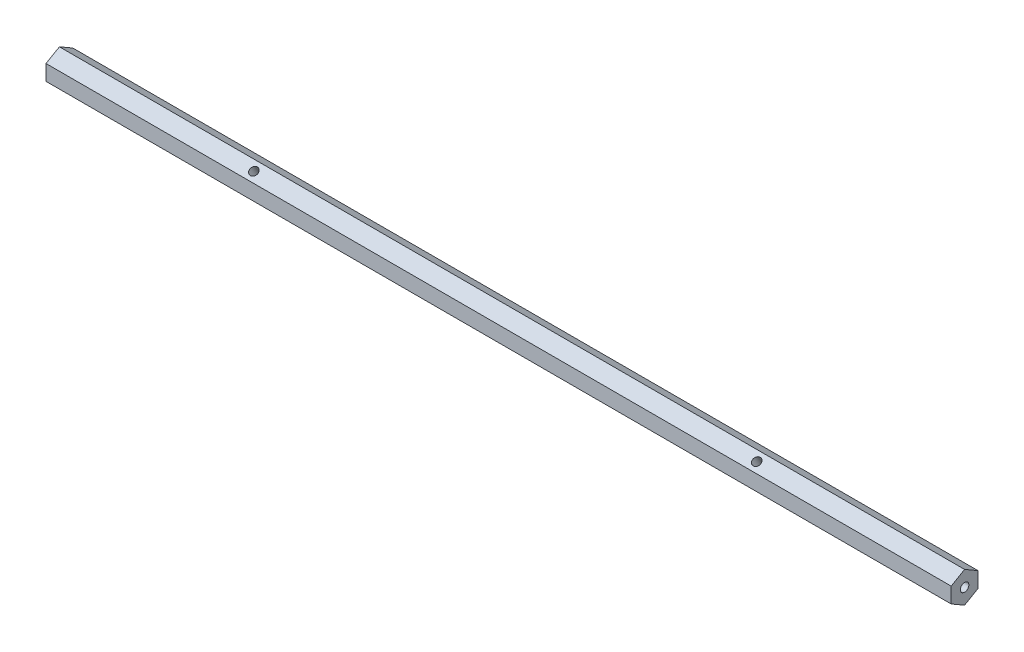
SolidWorks part; units mm, degrees
material "6061-T6 (SS)"
ref_plane "Front" through (0, 0, 0) normal (0, 0, 1) x (1, 0, 0)
ref_plane "Top" through (0, 0, 0) normal (0, 1, 0) x (1, 0, 0)
ref_plane "Right" through (0, 0, 0) normal (1, 0, 0) x (0, 0, -1)
ref_axis "Axis1" through (-80.9, 0, 0) along (1, 0, 0)
sketch "Sketch1" plane through (0, 0, 0) normal (1, 0, 0) x (0, 0, -1)
  line L1 (0, 7.3323) -> (-6.35, 3.6662)
  line L2 (-6.35, 3.6662) -> (-6.35, -3.6662)
  line L3 (-6.35, -3.6662) -> (0, -7.3323)
  line L4 (0, -7.3323) -> (6.35, -3.6662)
  line L5 (6.35, -3.6662) -> (6.35, 3.6662)
  line L6 (6.35, 3.6662) -> (0, 7.3323)
  circle A0 centre (0, 0) radius 6.35 construction
  dimension "D1" = 12.7
extrude "Boss-Extrude1" add sketch "Sketch1" along normal up to surface (428.625 mm away)
hole_wizard "#10-32 Tapped Hole1" positions "Sketch2" profile "Sketch3" tap size "#10-32" standard "ANSI Inch"
sketch "Sketch2" plane through (428.625, 0, 0) normal (1, 0, 0) x (0, 0, -1)
  point P0 (0, 0)
sketch "Sketch3" plane through (428.625, 0, 0) normal (0, 1, 0) x (0, 0, -1)
  line L0 (0, 0) -> (0, 13.2529)
  line L1 (0, 13.2529) -> (2.0193, 12.0396)
  line L2 (2.0193, 12.0396) -> (2.0193, 0)
  line L5 (2.0193, 0) -> (0, 0)
  line L10 (0, 13.2529) -> (-2.0193, 12.0396) construction
  line L11 (0, -6.35) -> (0, 107.95) construction
  dimension "Tap Drill Dia." = 4.0386
  dimension "Tap Drill Depth" = 12.0396
  dimension "Drill Angle" = 118
cosmetic thread "Hole Thread1" parameters "D1"=9.652, "D2"=4.826
hole_wizard "#10-32 Tapped Hole2" positions "Sketch4" profile "Sketch5" tap size "#10-32" standard "ANSI Inch"
sketch "Sketch4" plane through (0, 0, 0) normal (-1, 0, 0) x (0, 0, 1)
  point P0 (0, 0)
sketch "Sketch5" plane through (0, 0, 0) normal (0, 1, 0) x (0, 0, 1)
  line L0 (0, 0) -> (0, 13.2529)
  line L1 (0, 13.2529) -> (2.0193, 12.0396)
  line L2 (2.0193, 12.0396) -> (2.0193, 0)
  line L5 (2.0193, 0) -> (0, 0)
  line L10 (0, 13.2529) -> (-2.0193, 12.0396) construction
  line L11 (0, -6.35) -> (0, 107.95) construction
  dimension "Tap Drill Dia." = 4.0386
  dimension "Tap Drill Depth" = 12.0396
  dimension "Drill Angle" = 118
cosmetic thread "Hole Thread2" parameters "D1"=9.652, "D2"=4.826
sketch "Sketch6" plane through (0, 5.4993, 3.175) normal (0, 0.866, 0.5) x (1, 0, 0)
  line L0 (0, 7.3323) -> (0, 3.6662) construction
  line L3 (0, 0) -> (95.25, 0) construction
  line L4 (0, 3.6662) -> (0, -3.6662) construction
  line L9 (333.375, 0) -> (428.625, 0) construction
  line L10 (428.625, -3.6662) -> (428.625, 3.6662) construction
  circle A0 centre (95.25, 0) radius 1.905
  circle A1 centre (333.375, 0) radius 1.905
  dimension "D1" = 3.81
  dimension "D2" = 95.25
extrude "Cut-Extrude1" cut sketch "Sketch6" against normal through all
